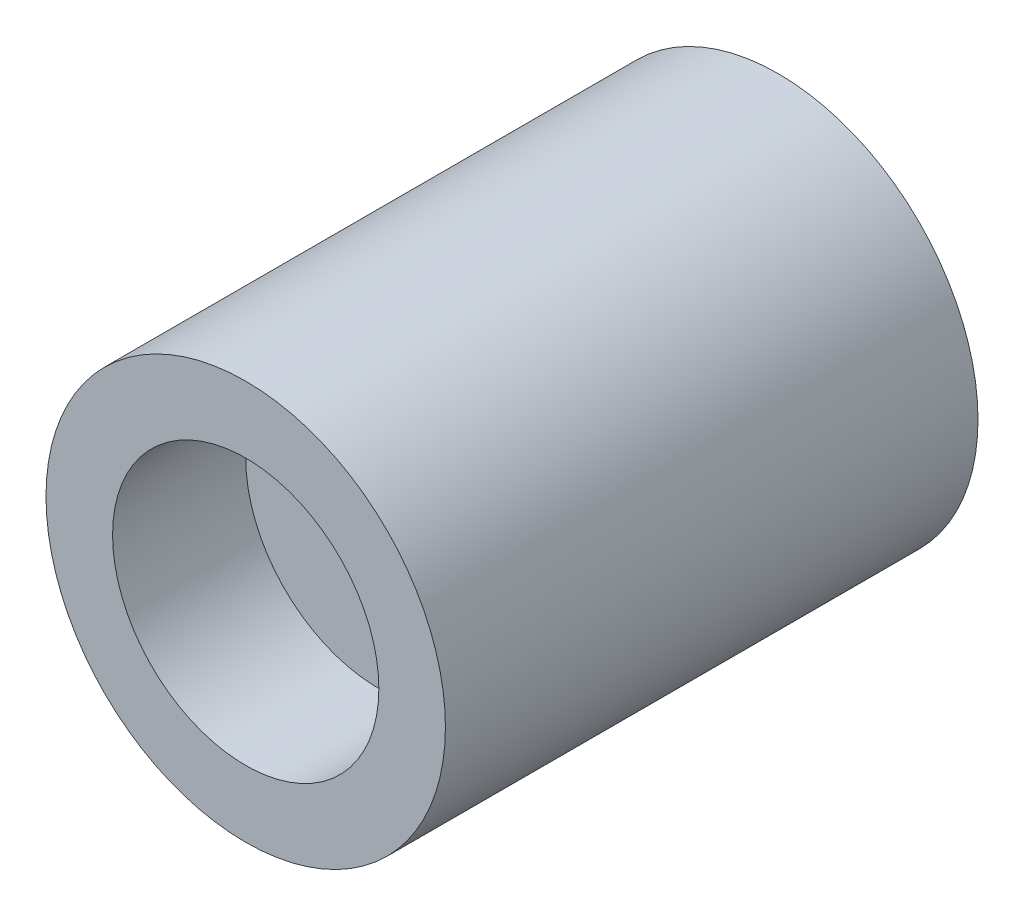
SolidWorks part; units mm, degrees
ref_plane "Front Plane" through (0, 0, 0) normal (1, 0, 0) x (0, 1, 0)
ref_plane "Top Plane" through (0, 0, 0) normal (0, 0, 1) x (0, 1, 0)
ref_plane "Right Plane" through (0, 0, 0) normal (0, 1, 0) x (-1, 0, 0)
sketch "Sketch1" plane through (0, 0, 0) normal (0, 0, 1) x (0, 1, 0)
  circle A0 centre (0, 0) radius 3
  circle A1 centre (0, 0) radius 1.2
  circle A2 centre (0, 0) radius 2
  dimension "D1" = 6
  dimension "ShaftDiameter" = 2.4
  dimension "D3" = 4
extrude "Boss-Extrude1" add sketch "Sketch1" along normal blind 8 contours A2 A1 | A0 A2 | A1 region at (0, -2.9151, 0) region at (0, 0, 0) region at (0, -1.9434, 0)
extrude "Cut-Extrude1" cut sketch "Sketch1<3>" against normal blind 2 from surface contours A2 A1 | A1 region at (0, 0, 0) region at (0, -1.9434, 0) starting at face at (3, 0, 8)
sketch "Sketch1<3>" plane through (0, 0, 0) normal (0, 0, 1) x (0, 1, 0) same geometry as "Sketch1"
extrude "Cut-Extrude2" cut sketch "Sketch1<4>" along normal blind 5 contours A1 region at (0, 0, 0)
sketch "Sketch1<4>" plane through (0, 0, 0) normal (0, 0, 1) x (0, 1, 0) same geometry as "Sketch1"
equation "\"MagnetDiameter\"= 4"
equation "\"BackShaftContainerDiameter\"=6"
equation "\"D3@Sketch1\"=\"MagnetDiameter\""
equation "\"D1@Sketch1\"=\"BackShaftContainerDiameter\""
equation "\"ShaftLength\"= 5"
equation "\"D1@Boss-Extrude1\"=\"ShaftLength\"+\"MagnetThickness\"+1"
equation "\"MagnetThickness\"=2"
equation "\"D1@Cut-Extrude1\"=\"MagnetThickness\""
equation "\"D1@Cut-Extrude2\"=\"ShaftLength\""
